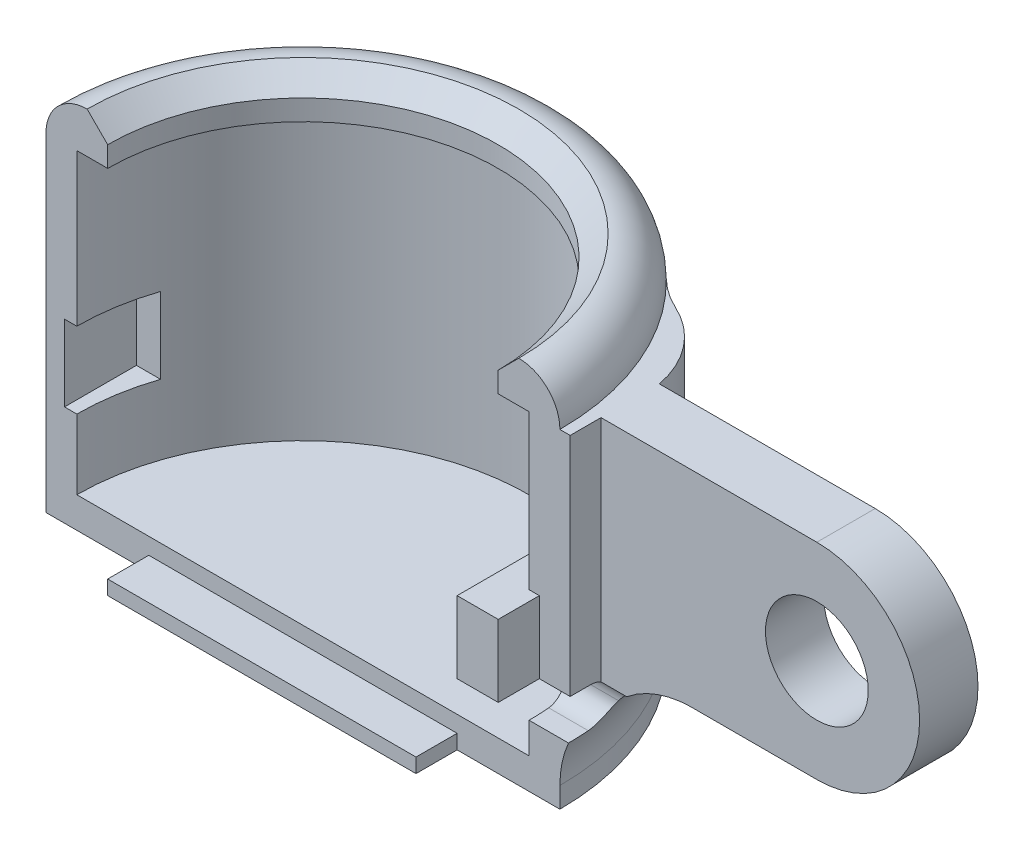
SolidWorks part; units mm, degrees
ref_plane "Plan de face" through (0, 0, 0) normal (0, 0, 1) x (1, 0, 0)
ref_plane "Plan de dessus" through (0, 0, 0) normal (0, 1, 0) x (1, 0, 0)
ref_plane "Plan de droite" through (0, 0, 0) normal (1, 0, 0) x (0, 0, -1)
sketch "Esquisse3" plane through (0, 0, 0) normal (0, 0, 1) x (1, 0, 0)
  line L0 (0, 0) -> (12.5, 0)
  line L1 (12.5, 0) -> (12.5, 18)
  line L2 (12.5, 18) -> (9.5, 18)
  line L3 (9.5, 18) -> (9.5, 16)
  line L4 (9.5, 16) -> (11, 16)
  line L5 (11, 16) -> (11, 1.5)
  line L6 (11, 1.5) -> (0, 1.5)
  line L7 (0, 1.5) -> (0, 0)
  line L8 (0, 0) -> (0, 28.6696) construction
  dimension "D1" = 19
  dimension "D2" = 25
  dimension "D3" = 14.5
  dimension "D4" = 2
  dimension "D5" = 1.5
  dimension "D6" = 22
revolve "Révolution1" add sketch "Esquisse3" angle 180 about L8
chamfer "Chanfrein1" distance 1 angle 45 1 edges at (0, 18, -9.5)
fillet "Congé1" radius 2 1 edges at (0, 18, -12.5)
sketch "Esquisse4" plane through (0, 0, 0) normal (1, 0, 0) x (0, 0, -1)
  line L0 (0, 0) -> (0, 3) construction
  line L1 (-2, 3) -> (2, 3)
  line L2 (-2, 3) -> (-2, 5)
  line L3 (-2, 5) -> (2, 5)
  line L4 (2, 3) -> (2, 5)
  dimension "D1" = 4
  dimension "D2" = 2
  dimension "D3" = 1.5
extrude "Enlèv. mat.-Extru.1" cut sketch "Esquisse4" along normal up to next
fillet "Congé2" radius 1 2 edges at (11.5778, 5, -2) (11.5778, 3, -2)
sketch "Esquisse5" plane through (0, 0, 0) normal (0, 0, 1) x (1, 0, 0)
  line L0 (11, 16) -> (11, 1.5) construction
  line L1 (9.5, 8.5) -> (11.5, 8.5)
  line L2 (9.5, 8.5) -> (9.5, 5)
  line L3 (9.5, 5) -> (11.5, 5)
  line L4 (11.5, 8.5) -> (11.5, 5)
  dimension "D1" = 3.5
  dimension "D2" = 2
  dimension "D3" = 1.5
  dimension "D4" = 3.5
extrude "Boss.-Extru.2" add sketch "Esquisse5" against normal up to surface and the other way blind 2 up to face at (6.0789, 6.0932, -2.9349)
sketch "Esquisse6" plane through (0, 0, 0) normal (0, 0, 1) x (1, 0, 0)
  line L0 (11.5, 8.5) -> (9.5, 8.5) construction
  line L1 (-11.5, 8.5) -> (-9.5, 8.5)
  line L2 (-11.5, 8.5) -> (-11.5, 5)
  line L3 (-11.5, 5) -> (-9.5, 5)
  line L4 (-9.5, 8.5) -> (-9.5, 5)
  line L5 (9.5, 8.5) -> (9.5, 5) construction
  line L6 (-12.5, 0) -> (-12.5, 16) construction
  line L8 (-11.6, 8.6) -> (-9.4, 8.6)
  line L9 (-11.6, 8.6) -> (-11.6, 4.9)
  line L10 (-11.6, 4.9) -> (-9.4, 4.9)
  line L11 (-9.4, 8.6) -> (-9.4, 4.9)
  dimension "D1" = 1
  dimension "D2" = 0.1
  dimension "D3" = 0.1
  dimension "D4" = 0.1
  dimension "D5" = 0.1
extrude "Enlèv. mat.-Extru.2" cut sketch "Esquisse6" against normal blind 3.5 contours L8 L11 L10 L9
sketch "Esquisse7" plane through (0, 0, 0) normal (0, -1, 0) x (1, 0, 0)
  line L2 (12.5, 0) -> (-12.5, 0) construction
  line L3 (7.5, 0) -> (-7.5, 0)
  line L4 (7.5, 0) -> (7.5, 2)
  line L5 (7.5, 2) -> (-7.5, 2)
  line L6 (-7.5, 0) -> (-7.5, 2)
  point P7 (0, 0)
  dimension "D1" = 15
  dimension "D2" = 2
extrude "Boss.-Extru.5" add sketch "Esquisse7" against normal blind 0.7
sketch "Esquisse9" plane through (0, 0, 0) normal (0, 0, 1) x (1, 0, 0)
  line L0 (12.5, 16) -> (23.5, 16)
  line L1 (12.5, 5) -> (12.5, 16) construction
  line L2 (23.5, 6) -> (12.5, 6)
  line L3 (12.5, 6) -> (12.5, 16)
  arc A0 (23.5, 16) -> (23.5, 6) centre (23.5, 11) cw
  circle A1 centre (23.5, 11) radius 2.5
  point P8 (22.5233, 5.6995)
  point P9 (0, 0)
  point P11 (21.4524, 11)
  dimension "D1" = 5
  dimension "D2" = 5
  dimension "D3" = 11
extrude "Boss.-Extru.6" add sketch "Esquisse9" against normal blind 7.5 separate body contours L0 A0 L2 L3 | A1
sketch "Esquisse10" plane through (0, 16, 0) normal (0, 1, 0) x (1, 0, 0)
  line L0 (12.5, 0) -> (23.5, 0) construction
  line L1 (13, 0) -> (28.5, 0)
  line L2 (13, 0) -> (13, 1.5)
  line L3 (13, 1.5) -> (28.5, 1.5)
  line L4 (28.5, 0) -> (28.5, 1.5)
  line L5 (28.5, 0) -> (28.5, 7.5) construction
  line L6 (12.5, 7.5) -> (23.5, 7.5) construction
  line L7 (13, 7.5) -> (28.5, 7.5)
  line L8 (13, 7.5) -> (13, 4.34)
  line L9 (13, 4.34) -> (28.5, 4.34)
  line L10 (28.5, 7.5) -> (28.5, 4.34)
  dimension "D1" = 1.5
  dimension "D2" = 3.16
  dimension "D3" = 15.5
extrude "Enlèv. mat.-Extru.3" cut sketch "Esquisse10" against normal up to next (10 mm away)
sketch "Esquisse11" plane through (12.5, 0, 0) normal (-1, 0, 0) x (0, 0, 1)
  line L1 (-7.5, 16) -> (0, 16)
  line L2 (-7.5, 16) -> (-7.5, 6)
  line L3 (-7.5, 6) -> (0, 6)
  line L4 (0, 16) -> (0, 6)
extrude "Boss.-Extru.7" add sketch "Esquisse11" along normal up to next contours L2 L1 L4 L3
fillet "Congé3" radius 5 1 edges at (10, 11, -7.5)
fillet "Congé4" radius 5 1 edges at (11.5239, 6, -4.8424)
fillet "Congé5" radius 5 1 edges at (13, 10.6675, -7.5)
